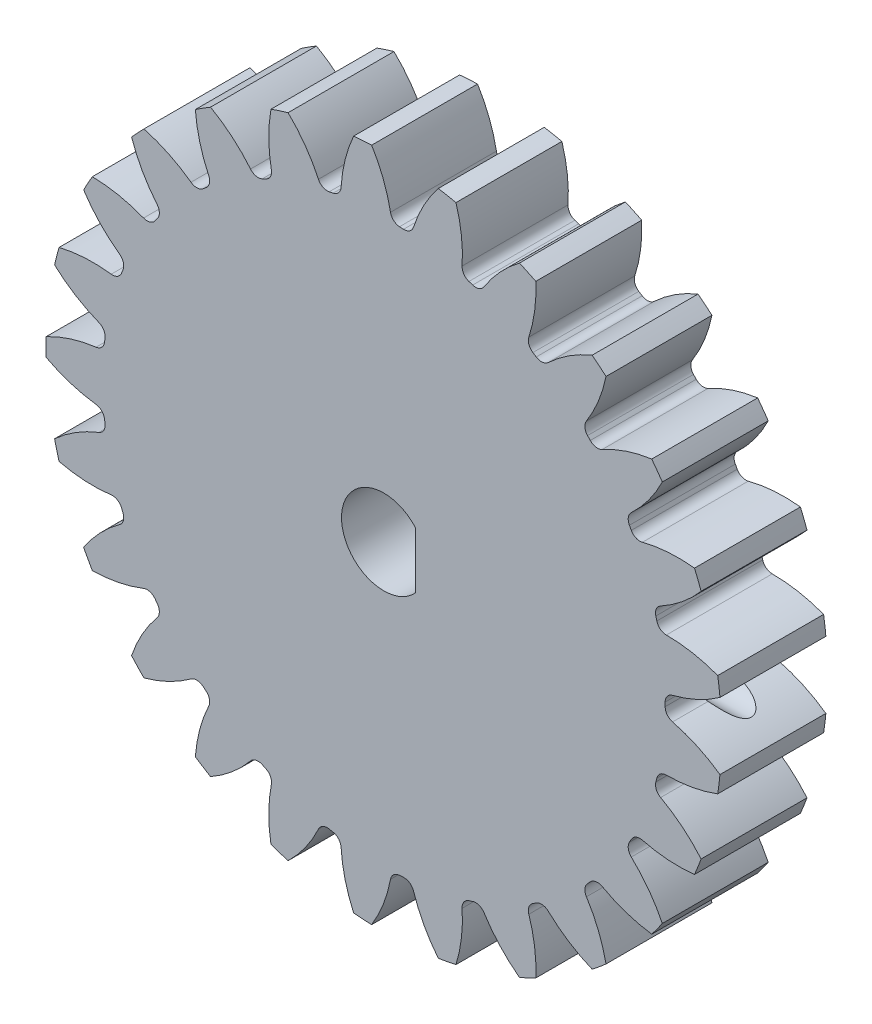
SolidWorks part; units mm, degrees
material "Delrin 2700 NC010, Low Viscosity Acetal Copolymer (SS)"
ref_plane "Front Plane" through (0, 0, 0) normal (0, 0, 1) x (1, 0, 0)
ref_plane "Top Plane" through (0, 0, 0) normal (0, 1, 0) x (1, 0, 0)
ref_plane "Right Plane" through (0, 0, 0) normal (1, 0, 0) x (0, 0, -1)
sketch "Sketch1" plane through (0, 0, 0) normal (0, 0, 1) x (1, 0, 0)
  line L0 (0, 0) -> (0, 18.75) construction
  line L1 (-6.0261, 20.9433) -> (6.0261, 16.5567) construction
  circle A0 centre (0, 0) radius 16.875 construction
  circle A1 centre (0, 0) radius 20.25 construction
  circle A2 centre (0, 0) radius 18.75 construction
  circle A3 centre (0, 0) radius 17.6192 construction
  circle A4 centre (0, 0) radius 15 construction
  circle A5 centre (0, 0) radius 4 construction
  point P8 (0.75, 0)
  point P13 (12.5, 0)
  dimension "OD" = 40.5
  dimension "Root Diameter" = 33.75
  dimension "Gear Pitch Diameter" = 37.5
  dimension "Base Diameter" = 35.2385
  dimension "Hub Diameter" = 30
  dimension "For Shaft Diameter" = 8
  dimension "Pressure Angle" = 20
  dimension "Number of Teeth" = 25
  dimension "Module" = 1.5
sketch "Sketch2" plane through (0, 0, 0) normal (1, 0, 0) x (0, 0, -1)
  line L0 (-14, 0) -> (6.35, 0) construction
  line L1 (6.35, 20.25) -> (6.35, -20.25) construction
  line L2 (0, -15) -> (-14, -15) construction
  line L3 (-14, 20.25) -> (6.35, 20.25) construction
  line L8 (-14, -15) -> (-14, 15) construction
  point P4 (0, 20.25)
  point P5 (-7, 0)
  dimension "Overall Width" = 20.35
  dimension "Hub Width" = 14
  dimension "Approx Set Screw Positon" = 7
  dimension "Face Width" = 6.35
sketch "Sketch3" plane through (0, 0, 0) normal (0, 0, 1) x (1, 0, 0)
  circle A0 centre (0, 0) radius 20.25
  circle A1 centre (0, 0) radius 20.25 construction
extrude "Boss-Extrude1" add sketch "Sketch3" against normal up to vertex (6.35 mm away) up to point (0, 0, -6.35)
sketch "Sketch4" plane through (0, 0, 0) normal (0, 0, 1) x (1, 0, 0)
  line L0 (16.8647, 0.589) -> (16.8647, -0.589)
  arc A3 (20.1508, 2.0016) -> (20.1508, -2.0016) centre (0, 0) cw
  circle A4 centre (0, 0) radius 20.25 construction
  arc A5 (16.8647, 0.589) -> (20.1508, 2.0016) centre (15.1691, 9.0626) ccw
  circle A8 centre (0, 0) radius 16.875 construction
  arc A9 (16.8647, -0.589) -> (20.1508, -2.0016) centre (15.1691, -9.0626) cw
  spline S0 degree 4 poles (17.599, 0.8441) (17.6032, 0.8444) (17.6149, 0.8452) (17.6369, 0.8475) (17.6729, 0.852) (17.7186, 0.859) (17.7776, 0.8695) (17.8468, 0.8838) (17.9227, 0.9015) (18.005, 0.9229) (18.0869, 0.946) (18.1684, 0.9709) (18.2492, 0.9972) (18.3469, 1.031) (18.4636, 1.074) (18.5994, 1.128) (18.7526, 1.1937) (18.9078, 1.2653) (19.0597, 1.3397) (19.2123, 1.4192) (19.3592, 1.4992) (19.5107, 1.5868) (19.65, 1.67) (19.8049, 1.7681) (19.9296, 1.8487) (20.0926, 1.9603) (20.1885, 2.0278) (20.3002, 2.1085) (20.3495, 2.1453) (20.3799, 2.168) knots 0 0 0 0 0 0.005377 0.015084 0.028532 0.04661 0.064855 0.092111 0.119476 0.146842 0.174209 0.201575 0.228941 0.256307 0.307035 0.361767 0.4165 0.471232 0.525964 0.580697 0.635429 0.690161 0.744894 0.799626 0.854358 0.909091 0.954545 1 1 1 1 1 construction
  spline S1 degree 4 poles (17.599, 0.8441) (17.6032, 0.8444) (17.6149, 0.8452) (17.6369, 0.8475) (17.6729, 0.852) (17.7186, 0.859) (17.7776, 0.8695) (17.8468, 0.8838) (17.9227, 0.9015) (18.005, 0.9229) (18.0869, 0.946) (18.1684, 0.9709) (18.2492, 0.9972) (18.3469, 1.031) (18.4636, 1.074) (18.5994, 1.128) (18.7526, 1.1937) (18.9078, 1.2653) (19.0597, 1.3397) (19.2123, 1.4192) (19.3592, 1.4992) (19.5107, 1.5868) (19.65, 1.67) (19.8049, 1.7681) (19.9296, 1.8487) (20.0572, 1.9361) (20.1192, 1.9793) (20.1508, 2.0016) knots 0 0 0 0 0 0.005377 0.015084 0.028532 0.04661 0.064855 0.092111 0.119476 0.146842 0.174209 0.201575 0.228941 0.256307 0.307035 0.361767 0.4165 0.471232 0.525964 0.580697 0.635429 0.690161 0.744894 0.799626 0.854358 0.909091 0.909091 0.909091 0.909091 0.909091 construction
  spline S2 degree 4 poles (17.599, -0.8441) (17.6032, -0.8444) (17.6149, -0.8452) (17.6369, -0.8475) (17.6729, -0.852) (17.7186, -0.859) (17.7776, -0.8695) (17.8468, -0.8838) (17.9227, -0.9015) (18.005, -0.9229) (18.0869, -0.946) (18.1684, -0.9709) (18.2492, -0.9972) (18.3469, -1.031) (18.4636, -1.074) (18.5994, -1.128) (18.7526, -1.1937) (18.9078, -1.2653) (19.0597, -1.3397) (19.2123, -1.4192) (19.3592, -1.4992) (19.5107, -1.5868) (19.65, -1.67) (19.8049, -1.7681) (19.9296, -1.8487) (20.0926, -1.9603) (20.1885, -2.0278) (20.3002, -2.1085) (20.3495, -2.1453) (20.3799, -2.168) knots 0 0 0 0 0 0.005377 0.015084 0.028532 0.04661 0.064855 0.092111 0.119476 0.146842 0.174209 0.201575 0.228941 0.256307 0.307035 0.361767 0.4165 0.471232 0.525964 0.580697 0.635429 0.690161 0.744894 0.799626 0.854358 0.909091 0.954545 1 1 1 1 1 construction
  spline S3 degree 4 poles (17.599, -0.8441) (17.6032, -0.8444) (17.6149, -0.8452) (17.6369, -0.8475) (17.6729, -0.852) (17.7186, -0.859) (17.7776, -0.8695) (17.8468, -0.8838) (17.9227, -0.9015) (18.005, -0.9229) (18.0869, -0.946) (18.1684, -0.9709) (18.2492, -0.9972) (18.3469, -1.031) (18.4636, -1.074) (18.5994, -1.128) (18.7526, -1.1937) (18.9078, -1.2653) (19.0597, -1.3397) (19.2123, -1.4192) (19.3592, -1.4992) (19.5107, -1.5868) (19.65, -1.67) (19.8049, -1.7681) (19.9296, -1.8487) (20.0572, -1.9361) (20.1192, -1.9793) (20.1508, -2.0016) knots 0 0 0 0 0 0.005377 0.015084 0.028532 0.04661 0.064855 0.092111 0.119476 0.146842 0.174209 0.201575 0.228941 0.256307 0.307035 0.361767 0.4165 0.471232 0.525964 0.580697 0.635429 0.690161 0.744894 0.799626 0.854358 0.909091 0.909091 0.909091 0.909091 0.909091 construction
  dimension "D1" = 1.1781
extrude "Cut-Extrude1" cut sketch "Sketch4" against normal through all both and the other way through all
fillet "Fillet1" radius 0.589 2 edges at (16.8647, 0.589, -3.175) (16.8647, -0.589, -3.175)
pattern_circular "CirPattern1" count 25 over 360 about axis through (0, 0, 14) along (0, 0, -1) of "Cut-Extrude1", "Fillet1"
sketch "Sketch5" plane through (0, 0, -6.35) normal (0, 0, -1) x (-1, 0, 0)
  line L0 (-1.905, 1.6801) -> (-1.905, -1.6801)
  line L1 (2.54, 8.0612) -> (2.54, -7.3153) construction
  arc A0 (-1.905, -1.6801) -> (-1.905, 1.6801) centre (0, 0) ccw
  dimension "D1" = 5.08
  dimension "D2" = 4.445
extrude "Cut-Extrude2" cut sketch "Sketch5" against normal through all
sketch "Sketch6" plane through (1.905, 0, 0) normal (-1, 0, 0) x (0, 0, 1)
  line L0 (0, -1.6801) -> (-6.35, -1.6801) construction
  circle A0 centre (-3.175, 0) radius 1.25
  point P6 (-3.175, -1.6801)
  dimension "D1" = 2.5
extrude "Cut-Extrude3" cut sketch "Sketch6" against normal through all
sketch "Sketch7" plane through (0, 0, 0) normal (0, 0, 1) x (1, 0, 0)
  circle A0 centre (0, 0) radius 18.75 construction
  dimension "D1" = 37.5
sketch "Sketch8" plane through (0, 0, 0) normal (0, 1, 0) x (1, 0, 0)
  line L0 (0, 0) -> (0, 12.6679) construction
  line L1 (-18.75, 0) -> (18.75, 0) construction
equation "\"Number of Teeth\"= 25"
equation "\"Module\"= 1.5"
equation "\"Diametral Pitch\"= 1 / \"Module\""
equation "\"Dedendum\"= 1.25 / \"Diametral Pitch\""
equation "\"Pitch Diameter\"= \"Module\" * \"Number of Teeth\""
equation "\"Root Diameter\"= \"Pitch Diameter\" - ( 2 * \"Dedendum\" )"
equation "\"Root Diameter@Sketch1\"=\"Root Diameter\""
equation "\"OD@Sketch1\" = \"Outside Diameter\""
equation "\"D1@CirPattern1\"=\"Number of Teeth\""
equation "\"Pressure Angle\"=20"
equation "\"Base Diameter\"= \"Pitch Diameter\" * cos ( \"Pressure Angle\" )"
equation "\"Outside Diameter\"= ( \"Number of Teeth\" + 2 ) / \"Diametral Pitch\""
equation "\"Pitch Angle\"= 360deg / \"Number of Teeth\""
equation "\"Alpha\"= sqr ( \"Pitch Diameter\" ^ 2 - \"Base Diameter\" ^ 2 ) / \"Base Diameter\" * 180 / PI - \"Pressure Angle\""
equation "\"Beta\"= ( \"Pitch Angle\" / 4 - \"Alpha\" )"
equation "\"Phi\"= sqr ( ( \"Outside Diameter\" / 2 ) ^ 2 - ( \"Base Diameter\" / 2 ) ^ 2 ) / ( \"Base Diameter\" / 2 )"
equation "\"Addendum\"= 1 / \"Diametral Pitch\""
equation "\"WorkingDepth\"= 2 / \"Diametral Pitch\""
equation "\"WholeDepth\"= 2.25 / \"Diametral Pitch\""
equation "\"Clearance\"= 0.25 / \"Diametral Pitch\""
equation "\"ToothThickness\"= ( pi * 2 ) / \"Diametral Pitch\""
equation "\"CircularPitch\"= pi / \"Diametral Pitch\""
equation "\"Number of Teeth@Sketch1\"=\"Number of Teeth\""
equation "\"Module@Sketch1\"=\"Module\""
equation "\"Pressure Angle@Sketch1\"=\"Pressure Angle\""
equation "\"Gear Pitch Diameter@Sketch1\"=\"Pitch Diameter\""
equation "\"Base Diameter@Sketch1\"=\"Base Diameter\""
equation "\"Fillet\"= \"Clearance\" * cos ( \"Pressure Angle\" ) * tan ( ( 90 + \"Pressure Angle\" ) / 2 )"
equation "\"D1\"= \"Fillet\""
equation "\"Approx Set Screw Positon@Sketch2\" = \"Hub Width@Sketch2\" / 2"
equation "\"D2\"= \"Fillet\" * 2"
equation "\"D1@Sketch4\"=\"CircularPitch\"*0.25"
equation "\"D1@Fillet1\"=\"CircularPitch\"*0.125"
equation "\"Overall Width@Sketch2\"=14mm+0.25in"
equation "\"D2@Sketch5\"=0.175in"
equation "\"D1@Sketch5\"=0.2in"
